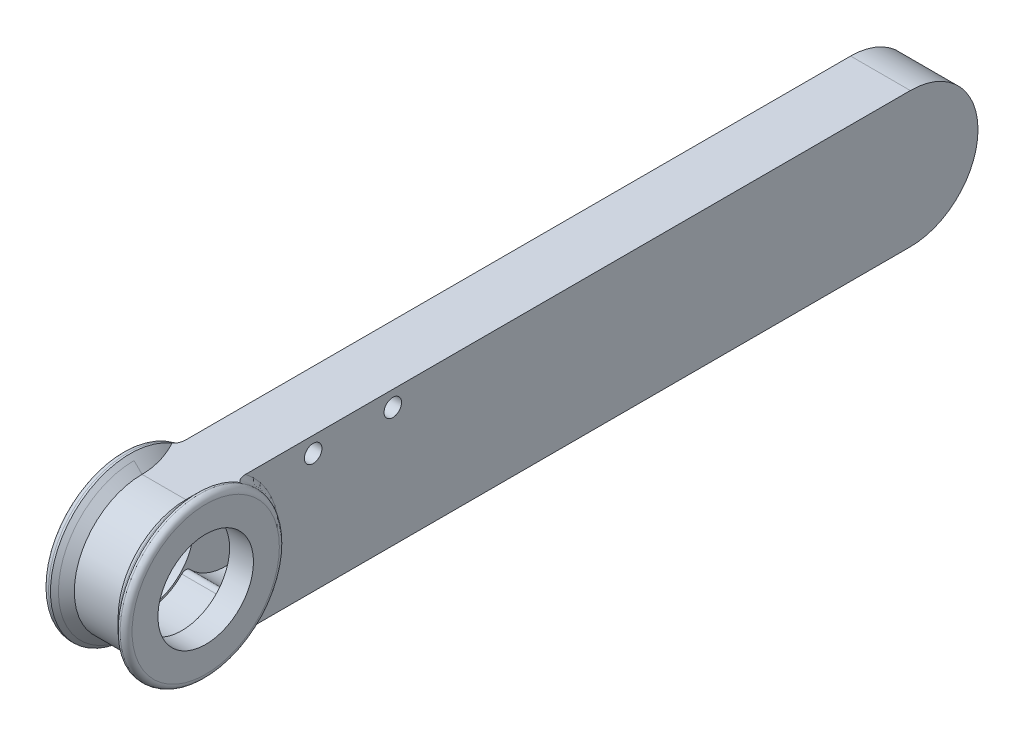
SolidWorks part; units mm, degrees
ref_plane "Front Plane" through (0, 0, 0) normal (0, 0, 1) x (1, 0, 0)
ref_plane "Top Plane" through (0, 0, 0) normal (0, 1, 0) x (1, 0, 0)
ref_plane "Right Plane" through (0, 0, 0) normal (1, 0, 0) x (0, 0, -1)
sketch "Sketch1" plane through (0, 0, 0) normal (1, 0, 0) x (0, 0, -1)
  line L0 (-45, 0) -> (45, 0) construction
  line L1 (-45, 8.5) -> (45, 8.5)
  line L2 (-45, -8.5) -> (45, -8.5)
  arc A0 (-45, 8.5) -> (-45, -8.5) centre (-45, 0) ccw
  arc A1 (45, -8.5) -> (45, 8.5) centre (45, 0) ccw
  circle A2 centre (-45, 0) radius 6
  point P3 (0, 0)
  point P10 (-49.1483, 0)
  dimension "D1" = 12
  dimension "D2" = 8.5
  dimension "D3" = 90
extrude "Boss-Extrude1" add sketch "Sketch1" along normal mid plane 7.5
sketch "Sketch2" plane through (0, 0, 0) normal (1, 0, 0) x (0, 0, -1)
  line L0 (-45, 0) -> (-35, 0) construction
  line L1 (-35, 0) -> (-25, 0) construction
  line L2 (-25, 0) -> (-15, 0) construction
  arc A0 (-40, 3.75) -> (-40, -3.75) centre (-45, 0) ccw
  arc A1 (-40, -3.75) -> (-30, -3.75) centre (-35, 0) ccw
  arc A2 (-30, -3.75) -> (-20, -3.75) centre (-25, 0) ccw
  arc A3 (-30, 3.75) -> (-40, 3.75) centre (-35, 0) ccw
  arc A4 (-20, -3.75) -> (-20, 3.75) centre (-15, 0) ccw
  arc A5 (-20, 3.75) -> (-30, 3.75) centre (-25, 0) ccw
  point P8 (-25, 0)
  point P12 (-20, -3.3136)
  dimension "D1" = 12.5
  dimension "D2" = 10
extrude "Cut-Extrude1" cut sketch "Sketch2" against normal mid plane 4.5
sketch "Sketch3" plane through (3.75, 0, 0) normal (1, 0, 0) x (0, 0, -1)
  circle A0 centre (-45, 0) radius 6
  circle A1 centre (-45, 0) radius 10
  circle A2 centre (-45, 0) radius 6 construction
  dimension "D1" = 20
extrude "Boss-Extrude2" add sketch "Sketch3" along normal blind 1.5
mirror "Mirror1" about plane through (0, 0, 0) normal (1, 0, 0) of "Boss-Extrude2"
chamfer "Chamfer1" distance 0.5 angle 45 2 edges at (-3.75, 0, 55) (3.75, 0, 55)
fillet "Fillet4" radius 0.75 2 edges at (-5.25, 0, 35) (5.25, 0, 35)
fillet "Fillet3" radius 0.7 2 edges at (-3.75, 0, 35) (3.75, 0, 35)
chamfer "Chamfer2" distance 1 angle 45 6 edges at (3.75, 8.5, 42.8787) (3.75, -8.5, 42.8787) (3.75, 0, 53.5) (-3.75, 8.5, 42.8787) (-3.75, -8.5, 42.8787) (-3.75, 0, 53.5)
sketch "Sketch4" plane through (3.75, 0, 0) normal (1, 0, 0) x (0, 0, -1)
  line L0 (45, 8.5) -> (-38.5008, 8.5) construction
  circle A0 centre (-30, 6.5275) radius 1.1
  circle A1 centre (-20, 6.5275) radius 1.1
  circle A2 centre (-45, 0) radius 6 construction
  circle A3 centre (-30, 6.5275) radius 1.9725 construction
  arc A4 (-20, 3.75) -> (-30, 3.75) centre (-25, 0) ccw construction
  point P12 (0, 0)
  dimension "D1" = 2.2
  dimension "D3" = 15
  dimension "D2" = 10
extrude "Cut-Extrude2" cut sketch "Sketch4" against normal through all both and the other way through all
fillet "Fillet5" radius 0.7 6 edges at (0, 3.75, 40) (0, 3.75, 30) (0, 3.75, 20) (0, -3.75, 20) (0, -3.75, 40) (0, -3.75, 30)
